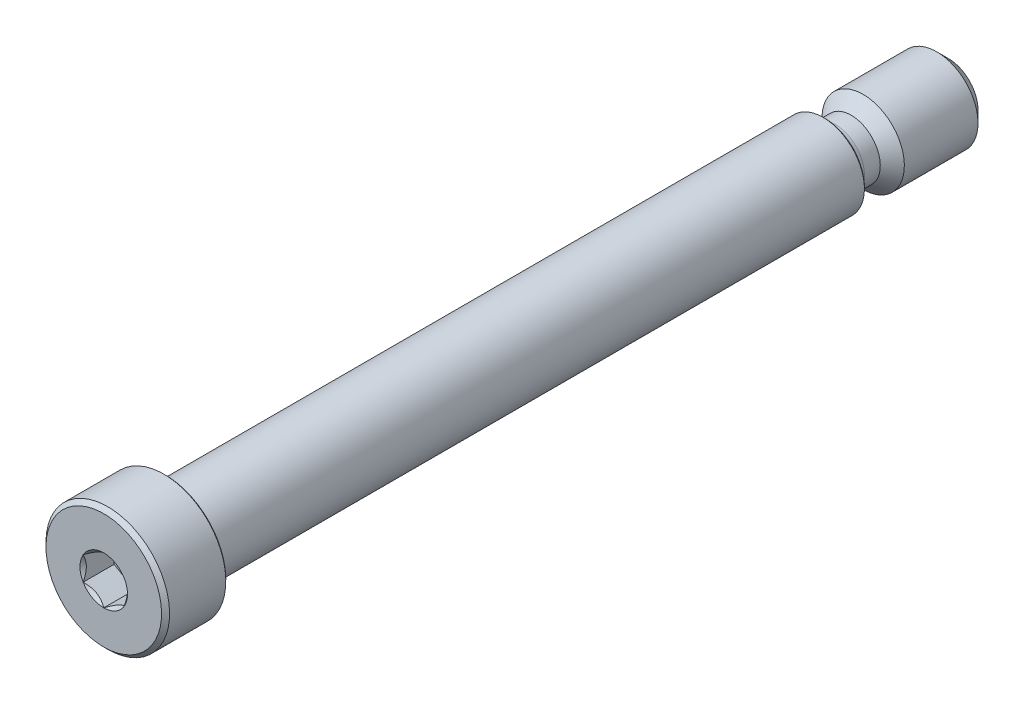
SolidWorks part; units mm, degrees
material "Cast Alloy Steel"
ref_plane "Front Plane" through (0, 0, 0) normal (0, 0, 1) x (1, 0, 0)
ref_plane "Top Plane" through (0, 0, 0) normal (0, 1, 0) x (1, 0, 0)
ref_plane "Right Plane" through (0, 0, 0) normal (1, 0, 0) x (0, 0, -1)
sketch "Sketch1" plane through (0, 0, 0) normal (1, 0, 0) x (0, 0, -1)
  line L0 (0, 0) -> (9.525, 0) construction
  line L1 (0, 0) -> (-50.8, 0) construction
  line L2 (9.525, 3.175) -> (9.525, -3.175) construction
  line L3 (9.4456, 3.3125) -> (10.7156, 3.3125) construction
  line L4 (10.7156, 3.3125) -> (10.0806, 2.2126) construction
  line L5 (10.0806, 2.2126) -> (9.4456, 3.3125) construction
  line L6 (9.4853, 3.2437) -> (10.6759, 3.2437) construction
  line L7 (9.525, 3.175) -> (10.6363, 3.175) construction
  line L8 (10.0012, 2.3501) -> (10.16, 2.3501) construction
  line L9 (10.0806, 2.3501) -> (10.0806, 2.2126) construction
  line L10 (10.0806, 3.175) -> (10.0806, 3.3125) construction
  line L11 (0, 3.175) -> (0, -3.175) construction
  line L12 (-50.8, 0) -> (-55.5625, 0) construction
  line L13 (-55.5625, 4.7625) -> (-55.5625, -4.7625) construction
  line L14 (-50.8, 4.7625) -> (-50.8, -4.7625) construction
  point P7 (9.525, 0)
  point P12 (6.35, -3.175)
  point P19 (10.0806, 3.2437)
  point P23 (0, 0)
  point P27 (-55.5625, 0)
  point P29 (-50.8, 0)
  point P30 (-55.5625, -1.5875)
  point P31 (-55.5625, 1.5875)
  point P32 (9.525, 3.175)
  point P33 (-53.1812, 0)
  point P34 (9.525, -3.175)
  dimension "Screw Size Decimal Equivalent" = 6.35
  dimension "D1" = 60
  dimension "Pitch" = 1.27
  dimension "D2" = 0.1588
  dimension "Thread Length" = 9.525
  dimension "D3" = 3.175
  dimension "Head Diameter" = 9.525
  dimension "Head Height" = 4.7625
  dimension "Shoulder Length" = 50.8
  dimension "Drive Size" = 3.175
  dimension "D4" = 2.3813
  dimension "Shoulder Diameter" = 6.35
sketch "Sketch2" plane through (0, 0, 0) normal (1, 0, 0) x (0, 0, -1)
  line L0 (0, 3.175) -> (2.9591, 3.175) construction
  line L1 (2.9591, 3.175) -> (2.032, 2.2479) construction
  line L2 (2.032, 2.2479) -> (0, 2.2479) construction
  line L3 (0, 0) -> (9.525, 0) construction
  line L4 (0, 0) -> (9.525, 0) construction
  line L6 (0, 3.175) -> (0, -3.175) construction
  dimension "Thread Neck (Undercut) Width/Length" = 2.032
  dimension "D3" = 45
  dimension "Thread Neck (Undercut) Diameter" = 4.4958
sketch "Sketch3" plane through (0, 0, 0) normal (1, 0, 0) x (0, 0, -1)
  line L0 (-55.5625, 4.4529) -> (-55.2529, 4.7625)
  line L1 (-55.5625, 4.7625) -> (-55.5625, -4.7625) construction
  line L2 (-55.2529, 4.7625) -> (-50.9191, 4.7625)
  line L3 (-50.9191, 4.7625) -> (-50.8, 4.6434)
  line L4 (-50.8, 4.6434) -> (-50.8, 3.175)
  line L5 (-55.5625, 4.4529) -> (-55.5625, 0)
  line L6 (-55.5625, 0) -> (-50.3238, 0)
  line L7 (0, 0) -> (-50.8, 0) construction
  line L8 (-50.3238, 0) -> (-50.3238, 3.175)
  line L9 (-50.3238, 3.175) -> (-50.8, 3.175)
  line L10 (0, 0) -> (-50.8, 0) construction
  dimension "D1" = 45
  dimension "D2" = 0.3096
  dimension "D3" = 45
  dimension "D4" = 0.1191
  dimension "D5" = 0.4763
  dimension "D6" = 6.35
revolve "Revolve1" add sketch "Sketch3" angle 360 about L6
fillet "Fillet1" radius 0.127 1 edges at (0, -3.175, 50.8)
sketch "Sketch4" plane through (0, 0, 0) normal (1, 0, 0) x (0, 0, -1)
  line L0 (-50.3238, 3.175) -> (-0.1191, 3.175)
  line L1 (0, 3.0559) -> (0, 0)
  line L2 (0, 0) -> (-50.3238, 0)
  line L3 (-50.3238, 0) -> (-50.3238, 3.175)
  line L4 (-0.1191, 3.175) -> (0, 3.0559)
  dimension "D1" = 45
  dimension "D2" = 0.1191
revolve "Revolve2" add sketch "Sketch4" angle 360 about L2
sketch "Sketch5" plane through (0, 0, 0) normal (1, 0, 0) x (0, 0, -1)
  line L0 (9.525, 2.286) -> (8.636, 3.175)
  line L1 (9.525, 3.175) -> (9.525, -3.175) construction
  line L2 (8.636, 3.175) -> (2.9591, 3.175)
  line L3 (2.9591, 3.175) -> (2.032, 2.2479)
  line L4 (2.032, 2.2479) -> (0.808, 2.2479)
  line L5 (0, 3.0559) -> (0, 0)
  line L6 (0, 3.175) -> (0, -3.175) construction
  line L7 (0, 0) -> (9.525, 0)
  line L8 (9.525, 0) -> (9.525, 2.286)
  line L9 (2.032, 2.2479) -> (0, 2.2479) construction
  arc A1 (0.808, 2.2479) -> (0, 3.0559) centre (0.808, 3.0559) cw
  dimension "D1" = 45
  dimension "D2" = 0.889
revolve "Revolve3" add sketch "Sketch5" angle 360 about L7
sketch "Sketch6" plane through (0, 0, 55.5625) normal (0, 0, 1) x (1, 0, 0)
  line L1 (-1.5875, 0.9165) -> (-1.5875, -0.9165)
  line L2 (-1.5875, -0.9165) -> (0, -1.8331)
  line L3 (0, -1.8331) -> (1.5875, -0.9165)
  line L4 (1.5875, -0.9165) -> (1.5875, 0.9165)
  line L5 (1.5875, 0.9165) -> (0, 1.8331)
  line L6 (0, 1.8331) -> (-1.5875, 0.9165)
  circle A0 centre (0, 0) radius 1.5875 construction
extrude "Cut-Extrude1" cut sketch "Sketch6" against normal up to vertex (2.3813 mm away) up to point (0, 0, 53.1812)
sketch "Sketch7" plane through (0, 0, 55.5625) normal (0, 0, 1) x (1, 0, 0)
  circle A0 centre (0, 0) radius 1.8331
extrude "Cut-Extrude2" cut sketch "Sketch7" against normal up to vertex (2.3813 mm away) draft 45 up to point (0, 0, 53.1812)
sketch "Sketch11" plane through (0, 0, 53.1812) normal (0, 0, 1) x (1, 0, 0)
  line L1 (-0.5556, 0.3208) -> (-0.5556, -0.3208)
  line L2 (-0.5556, -0.3208) -> (0, -0.6416)
  line L3 (0, -0.6416) -> (0.5556, -0.3208)
  line L4 (0.5556, -0.3208) -> (0.5556, 0.3208)
  line L5 (0.5556, 0.3208) -> (0, 0.6416)
  line L6 (0, 0.6416) -> (-0.5556, 0.3208)
  circle A0 centre (0, 0) radius 0.5556 construction
  dimension "D1" = 1.1113
extrude "Cut-Extrude4" cut sketch "Sketch11" against normal blind 1.1906 draft 45
sketch "Sketch12" plane through (0, 0, 0) normal (1, 0, 0) x (0, 0, -1)
  line L0 (-38.1, 4.7625) -> (-38.1, -4.7625) construction
  line L2 (-12.7, 4.7625) -> (-12.7, -4.7625) construction
  line L4 (-50.8, 4.7625) -> (-50.8, -4.7625) construction
  line L5 (0, 0) -> (-50.8, 0) construction
  line L7 (0, 3.175) -> (0, -3.175) construction
  point P3 (-38.1, 0)
  point P6 (-12.7, 0)
  dimension "D1" = 12.7
  dimension "D2" = 12.7
sketch "Sketch13" plane through (0, 0, 0) normal (0, 0, 1) x (1, 0, 0)
  circle A0 centre (0, 0) radius 4.7625 construction
sketch "Sketch8" [suppressed] plane through (0, 0, 0) normal (1, 0, 0) x (0, 0, -1)
  line L0 (9.4853, 3.2437) -> (10.6759, 3.2437)
  line L1 (10.6759, 3.2437) -> (10.16, 2.3501)
  line L2 (10.16, 2.3501) -> (10.0012, 2.3501)
  line L3 (10.0012, 2.3501) -> (9.4853, 3.2437)
sketch "Sketch9" [suppressed] plane through (0, 0, -9.525) normal (0, 0, -1) x (-1, 0, 0)
  circle A0 centre (0, 0) radius 3.175
curve "Helix/Spiral1" [suppressed] pitch 1.27 height 9.525 turns 7.5
sweep "Cut-Sweep1" [suppressed] cut profiles "Sketch8" path "Helix/Spiral1"
ref_plane "Plane1" [suppressed] through (0, 0, 55.3303) normal (0, 0, 1) x (1, 0, 0)
sketch "Sketch10" [suppressed] plane through (0, 0, 55.3303) normal (0, 0, 1) x (1, 0, 0)
  line L0 (-0.143, 4.7625) -> (0.143, 4.7625)
  line L1 (-0.143, 4.7625) -> (0, 4.5149)
  line L2 (0, 4.5149) -> (0.143, 4.7625)
  line L3 (-0.143, 4.7625) -> (0, 0) construction
  line L4 (0, 0) -> (0.143, 4.7625) construction
  circle A0 centre (0, 0) radius 4.5149 construction
  point P7 (0, 4.7625)
  dimension "D1" = 0.2476
  dimension "D2" = 3.439
extrude "Cut-Extrude3" [suppressed] cut sketch "Sketch10" against normal blind 3.81
pattern_circular "CirPattern1" [suppressed] count 85 over 360 about axis through (0, 0, 50.8) along (0, 0, 1) reverse direction yes of bodies 110
equation "\"D2@Sketch1\"=\"Pitch@Sketch1\"/8"
equation "\"D3@Sketch1\"=\"Pitch@Sketch1\"*2.5"
equation "\"D4@Sketch1\"=\"Head Height@Sketch1\"*.5"
equation "\"D2@Sketch3\"=\"Head Height@Sketch1\" * .065"
equation "\"D4@Sketch3\" = \"Head Height@Sketch1\" * .025"
equation "\"D5@Sketch3\"=\"Head Height@Sketch1\"*.1"
equation "\"D1@Fillet1\"=\"Shoulder Diameter@Sketch1\"*.02"
equation "\"D2@Sketch5\"=\"Pitch@Sketch1\"*.7"
equation "\"D2@Sketch4\"=\"D4@Sketch3\""
equation "\"D3@Helix/Spiral1\"=\"Thread Length@Sketch1\""
equation "\"D4@Helix/Spiral1\"=\"Pitch@Sketch1\""
equation "\"D1@Sketch10\"=\"D2@Sketch3\"*.8"
equation "\"D1@Cut-Extrude3\"=\"Head Height@Sketch1\"*.8"
equation "\"D1@CirPattern1\"=(360/\"D2@Sketch10\")-20"
equation "\"D1@Plane1\"=\"D2@Sketch3\"*.75"
equation "\"D1@Sketch11\"=\"Drive Size@Sketch1\"*.35"
equation "\"D1@Cut-Extrude4\"=\"Head Height@Sketch1\"*.25"
equation "\"D1@Sketch12\"=\"Shoulder Length@Sketch1\"*.25"
equation "\"D2@Sketch12\"=\"D1@Sketch12\""
equation "\"D6@Sketch3\"=\"Shoulder Diameter@Sketch1\""
